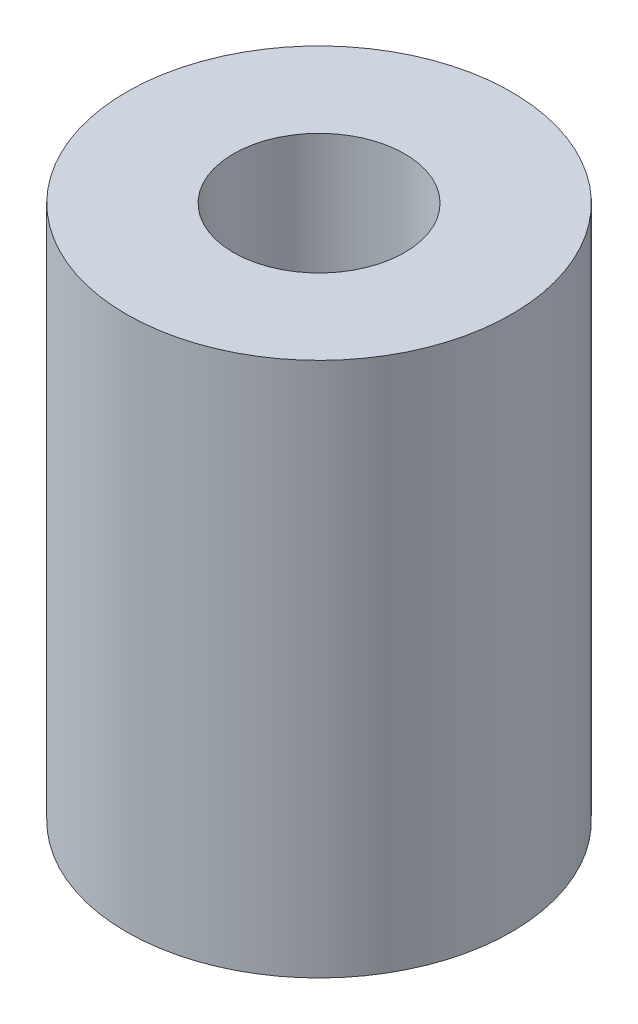
SolidWorks part; units mm, degrees
ref_plane "Front Plane" through (0, 0, 0) normal (0, 0, 1) x (1, 0, 0)
ref_plane "Top Plane" through (0, 0, 0) normal (0, 1, 0) x (1, 0, 0)
ref_plane "Right Plane" through (0, 0, 0) normal (1, 0, 0) x (0, 0, -1)
sketch "Sketch1" plane through (0, 0, 0) normal (0, 1, 0) x (1, 0, 0)
  circle A0 centre (0, 0) radius 9
  dimension "D1" = 18
extrude "Boss-Extrude1" add sketch "Sketch1" along normal mid plane 25
sketch "Sketch2" plane through (0, 12.5, 0) normal (0, 1, 0) x (1, 0, 0)
  circle A0 centre (0, 0) radius 4
  dimension "D1" = 8
extrude "Cut-Extrude1" cut sketch "Sketch2" against normal up to surface (12.5 mm away) up to plane "Top Plane"
sketch "Sketch3" plane through (0, -12.5, 0) normal (0, -1, 0) x (1, 0, 0)
  circle A0 centre (0, 0) radius 2.5
  dimension "D1" = 5
extrude "Cut-Extrude2" cut sketch "Sketch3" against normal up to surface (12.5 mm away) up to plane "Top Plane"
ref_axis "Shaft Axis" through (0, 12.5, 0) along (0, -1, 0)
